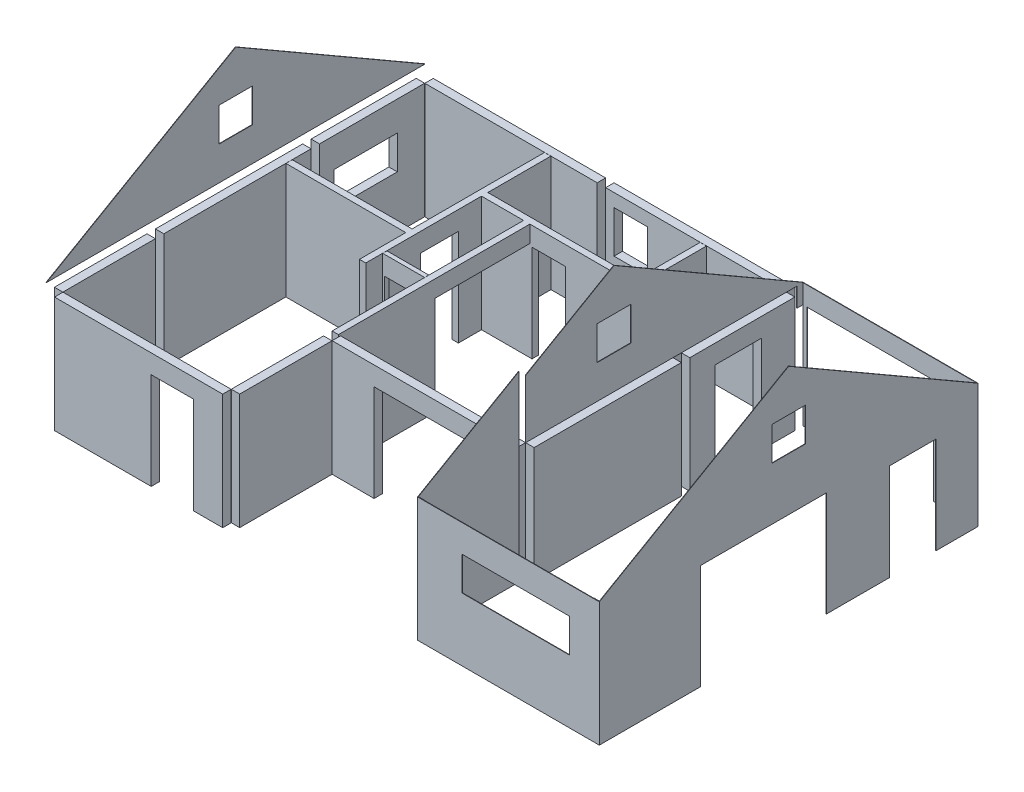
SolidWorks part; units mm, degrees
ref_plane "Спереди" through (0, 0, 0) normal (0, 0, 1) x (1, 0, 0)
ref_plane "Сверху" through (0, 0, 0) normal (0, 1, 0) x (1, 0, 0)
ref_plane "Справа" through (0, 0, 0) normal (1, 0, 0) x (0, 0, -1)
sketch "Эскиз1" plane through (0, 0, 0) normal (0, 1, 0) x (1, 0, 0)
  line L0 (9000, -6600) -> (4400, -6600) construction
  line L1 (0, 0) -> (9000, 0) construction
  line L2 (0, 0) -> (0, -8800) construction
  line L3 (0, -9000) -> (4400, -9000) construction
  line L4 (9000, 0) -> (9000, -6600) construction
  line L5 (4400, -6600) -> (4400, -9000) construction
  line L6 (8800, -203) -> (9000, -203)
  line L7 (203, 0) -> (4300, 0)
  line L8 (203, 0) -> (203, -200)
  line L9 (203, -200) -> (4300, -200)
  line L12 (0, -200) -> (0, -2700)
  line L14 (200, -200) -> (200, -2700)
  line L15 (203, -9000) -> (2500, -9000)
  line L16 (203, -9000) -> (203, -8800)
  line L17 (203, -8800) -> (2500, -8800)
  line L19 (4400, -8797) -> (4200, -8797)
  line L20 (4400, -8797) -> (4400, -6603)
  line L22 (4200, -8797) -> (4200, -6603)
  line L24 (9000, -203) -> (9000, -1000)
  line L26 (8800, -203) -> (8800, -1000)
  line L27 (8797, -6600) -> (7597, -6600)
  line L28 (8797, -6600) -> (8797, -6400)
  line L29 (8797, -6400) -> (7597, -6400)
  line L31 (2500, -8800) -> (2500, -9000)
  line L32 (3500, -8800) -> (3500, -9000)
  line L33 (3500, -8800) -> (4200, -8800)
  line L34 (3500, -9000) -> (4200, -9000)
  line L35 (5597, -6400) -> (5597, -6600)
  line L36 (7597, -6400) -> (7597, -6600)
  line L37 (5597, -6400) -> (4400, -6400)
  line L38 (5597, -6600) -> (4400, -6600)
  line L39 (8800, -1000) -> (9000, -1000)
  line L41 (8800, -2100) -> (9000, -2100)
  line L42 (8800, -2100) -> (8800, -2700)
  line L43 (9000, -2100) -> (9000, -2700)
  line L47 (4200, -6400) -> (4350, -6400)
  line L83 (4200, -6603) -> (4400, -6603)
  line L92 (4200, -4100) -> (4350, -4100)
  line L93 (4200, -4100) -> (4200, -6400)
  line L94 (4350, -4100) -> (4350, -6400)
  line L100 (200, -8800) -> (0, -8800)
  line L101 (4200, -8800) -> (4200, -9000)
  line L102 (4400, -6400) -> (4400, -6600)
  line L103 (8800, -6400) -> (9000, -6400)
  line L104 (0, -200) -> (200, -200)
  line L108 (0, -4500) -> (0, -6400)
  line L109 (200, -4500) -> (200, -6400)
  line L110 (8800, 0) -> (8800, -200)
  line L111 (4300, 0) -> (4300, -200)
  line L113 (4500, 0) -> (4500, -200)
  line L114 (4500, 0) -> (8800, 0)
  line L115 (4500, -200) -> (8800, -200)
  line L116 (0, -9000) -> (0, -8800) construction
  line L117 (-6170.9643, 0) -> (12200, 0) construction
  line L118 (0, 1882.3698) -> (0, -11726.3327) construction
  line L119 (-6170.9643, -4500) -> (10764.3505, -4500) construction
  line L120 (1000, -4500) -> (2250, -4500) construction
  line L121 (-6170.9643, -9000) -> (12200, -9000) construction
  line L122 (1000, -4500) -> (1000, -4600) construction
  line L123 (1000, -4600) -> (2250, -4600) construction
  line L124 (2250, -4500) -> (2250, -4600) construction
  line L125 (1000, -4500) -> (2250, -4600) construction
  line L126 (1000, -4600) -> (2250, -4500) construction
  line L131 (0, -2700) -> (200, -2700)
  line L132 (0, -2900) -> (0, -4500)
  line L137 (3050, -203) -> (3200, -203)
  line L138 (3050, -203) -> (3050, -2400)
  line L139 (3050, -2400) -> (3200, -2400)
  line L140 (3200, -203) -> (3200, -1700)
  line L141 (3050, -203) -> (3200, -2400) construction
  line L142 (3050, -2400) -> (3200, -203) construction
  line L143 (3050, -3300) -> (3200, -3300)
  line L144 (3050, -3300) -> (3050, -3350)
  line L145 (3050, -4600) -> (3200, -4600)
  line L146 (3200, -3300) -> (3200, -4600)
  line L147 (3050, -3300) -> (3200, -4600) construction
  line L148 (3050, -4600) -> (3200, -3300) construction
  line L149 (4150, -4100) -> (4197, -4100)
  line L150 (4150, -4100) -> (4150, -4200)
  line L151 (4150, -4200) -> (4197, -4200)
  line L152 (4197, -4100) -> (4197, -4200)
  line L153 (4150, -4100) -> (4197, -4200) construction
  line L154 (4150, -4200) -> (4197, -4100) construction
  line L155 (203, -3350) -> (3050, -3350)
  line L156 (203, -3350) -> (203, -3500)
  line L157 (203, -3500) -> (3050, -3500)
  line L159 (203, -3350) -> (3050, -3500) construction
  line L160 (203, -3500) -> (3050, -3350) construction
  line L161 (6400, -3500) -> (8800, -3500) construction
  line L162 (4400, 2182.3698) -> (4400, -11426.3327) construction
  line L163 (5200, -1700) -> (6750, -1700)
  line L164 (9000, 2182.3698) -> (9000, -11265.4622) construction
  line L165 (5200, -1700) -> (5200, -1850)
  line L166 (5200, -1850) -> (6900, -1850)
  line L167 (6900, -1700) -> (6900, -1850)
  line L168 (5200, -1700) -> (6900, -1850) construction
  line L169 (5200, -1850) -> (6900, -1700) construction
  line L170 (5800, -2800) -> (8797, -2800) construction
  line L171 (5800, -2800) -> (5800, -2900) construction
  line L172 (5800, -2900) -> (8797, -2900) construction
  line L173 (8797, -2800) -> (8797, -2900) construction
  line L174 (5800, -2800) -> (8797, -2900) construction
  line L175 (5800, -2900) -> (8797, -2800) construction
  line L176 (6750, -203) -> (6900, -203)
  line L177 (6750, -203) -> (6750, -1700)
  line L179 (6900, -203) -> (6900, -1700)
  line L180 (6750, -203) -> (6900, -1700) construction
  line L181 (6750, -1700) -> (6900, -203) construction
  line L186 (3200, -1700) -> (4400, -1700)
  line L188 (3200, -1850) -> (4400, -1850)
  line L189 (4400, -1700) -> (4400, -1850)
  line L190 (3200, -1700) -> (4400, -1850) construction
  line L191 (3200, -1850) -> (4400, -1700) construction
  line L192 (5800, -2900) -> (6400, -2900) construction
  line L193 (5800, -2900) -> (5800, -3500) construction
  line L194 (5800, -3500) -> (6400, -3500) construction
  line L195 (6400, -2900) -> (6400, -3500) construction
  line L196 (5800, -2900) -> (6400, -3500) construction
  line L197 (5800, -3500) -> (6400, -2900) construction
  line L198 (12200, 0) -> (12200, -9000) construction
  line L199 (5350, -4400) -> (5800, -3500) construction
  line L204 (3203, -4100) -> (3250, -4100)
  line L205 (3203, -4100) -> (3203, -4200)
  line L206 (3203, -4200) -> (3250, -4200)
  line L207 (3250, -4100) -> (3250, -4200)
  line L208 (3203, -4100) -> (3250, -4200) construction
  line L209 (3203, -4200) -> (3250, -4100) construction
  line L210 (4350, -4400) -> (5350, -4400) construction
  line L211 (4350, -4400) -> (4350, -6400) construction
  line L212 (4350, -6400) -> (5350, -6400) construction
  line L213 (5350, -4400) -> (5350, -6400) construction
  line L214 (4350, -4400) -> (5350, -6400) construction
  line L215 (4350, -6400) -> (5350, -4400) construction
  line L216 (3200, -1850) -> (3200, -2400)
  line L217 (0, -2900) -> (200, -2900)
  line L218 (200, -2900) -> (200, -4500)
  line L219 (0, -6400) -> (200, -6400)
  line L220 (0, -6600) -> (0, -8800)
  line L221 (0, -6600) -> (200, -6600)
  line L222 (200, -6600) -> (200, -8800)
  line L223 (3050, -3500) -> (3050, -4600)
  line L224 (8800, -2700) -> (9000, -2700)
  line L225 (8800, -2900) -> (8800, -6400)
  line L226 (8800, -2900) -> (9000, -2900)
  line L227 (9000, -2900) -> (9000, -6400)
  point P14 (3226.5, -4150)
  point P17 (7298.5, -2850)
  point P41 (1625, -4550)
  point P52 (3125, -1301.5)
  point P62 (3125, -3950)
  point P67 (4173.5, -4150)
  point P72 (1626.5, -3425)
  point P103 (3800, -1775)
  point P104 (6825, -951.5)
  point P105 (4150, -4150)
  point P108 (6050, -1775)
  point P120 (6750, -951.5)
  point P122 (6100, -3200)
  point P127 (4850, -5400)
  dimension "D2" = 6600
  dimension "D3" = 9000
  dimension "D4" = 200
  dimension "D5" = 3
  dimension "D6" = 3
  dimension "D7" = 3
  dimension "D8" = 9000
  dimension "D9" = 200
  dimension "D10" = 3
  dimension "D11" = 3
  dimension "D12" = 700
  dimension "D13" = 50
  dimension "D14" = 4500
  dimension "D15" = 4000
  dimension "D16" = 100
  dimension "D17" = 800
  dimension "D18" = 4400
  dimension "D19" = 4600
  dimension "D20" = 1000
  dimension "D21" = 800
  dimension "D22" = 2000
  dimension "D23" = 1200
  dimension "D24" = 1100
  dimension "D25" = 3
  dimension "D26" = 200
  dimension "D27" = 1000
  dimension "D29" = 200
  dimension "D30" = 4500
  dimension "D31" = 3
  dimension "D32" = 200
  dimension "D33" = 3
  dimension "D34" = 900
  dimension "D35" = 3
  dimension "D36" = 900
  dimension "D37" = 50
  dimension "D38" = 150
  dimension "D39" = 100
  dimension "D40" = 3
  dimension "D41" = 2850
  dimension "D42" = 3150
  dimension "D43" = 1250
  dimension "D44" = 200
  dimension "D46" = 3550
  dimension "D47" = 1500
  dimension "D48" = 800
  dimension "D49" = 1900
  dimension "D50" = 950
  dimension "D51" = 3
  dimension "D53" = 800
  dimension "D54" = 3
  dimension "D55" = 4450
  dimension "D56" = 3500
  dimension "D57" = 2400
  dimension "D58" = 3000
  dimension "D59" = 1400
  dimension "D60" = 2650
  dimension "D61" = 600
  dimension "D63" = 2900
  dimension "D64" = 2300
  dimension "D65" = 1247
  dimension "D66" = 3200
  dimension "D67" = 2000
  dimension "D68" = 1000
  dimension "D72" = 200
extrude "Бобышка-Вытянуть3" add sketch "Эскиз1" along normal blind 2750 contours L155 | L42 L103 L43 L41 | L26 L39 L24 L6 | L113 L115 L110 L114 | L216 L188 L189 L186 L140 L137 L138 L139 | L179 L176 L177 L163 L165 L166 L167 | L157 L223 L145 L146 L143 L144 L155 L156 | L108 L219 L109 L218 L217 L132 | L222 L221 L220 L100 | L144 L145 L146 L143 | L140 L139 L138 L137 | L27 L36 L29 L28 | L8 L9 L111 L7 | L14 L131 L12 L104 | L100 L108 L132 L217 L218 L109 | L47 L94 L92 L93 | L35 L38 L102 L37 | L171 L172 L173 L170 | L19 L22 L83 L20 | L32 L34 L101 L33 | L15 L31 L17 L16 | L122 L120 L124 L123 | L205 L204 L207 L206 | L150 L149 L152 L151 | L165 L163 L167 L166 | L103 L227 L226 L225 region at (8900, 0, 601.5) region at (8900, 0, 2400) region at (100, 0, 7700) region at (100, 0, 4650) region at (6650, 0, 100) region at (3125, 0, 228.7863) region at (3125, 0, 3332.668) region at (5975, 0, 1723.6698)
sketch "Эскиз2" plane through (0, 0, 0) normal (-1, 0, 0) x (0, 0, 1)
  line L2 (850, 1250) -> (2350, 1250)
  line L3 (850, 1250) -> (850, 2050)
  line L4 (850, 2050) -> (2350, 2050)
  line L5 (2350, 1250) -> (2350, 2050)
  line L7 (200, 0) -> (2700, 0) construction
  line L8 (3350, 2750) -> (3350, 0) construction
  dimension "D1" = 1500
  dimension "D2" = 800
  dimension "D3" = 1250
  dimension "D4" = 1000
extrude "Вырез-Вытянуть2" cut sketch "Эскиз2" against normal blind 250
sketch "Эскиз3" plane through (0, 0, 0) normal (0, 0, -1) x (-1, 0, 0)
  line L0 (-4500, 0) -> (-8800, 0) construction
  line L8 (-5500, 2440) -> (-4700, 2440)
  line L9 (-5500, 2440) -> (-5500, 1440)
  line L10 (-5500, 1440) -> (-4700, 1440)
  line L11 (-4700, 2440) -> (-4700, 1440)
  line L15 (-4500, 2750) -> (-4500, 0) construction
  dimension "D1" = 200
  dimension "D2" = 2440
  dimension "D3" = 800
  dimension "D4" = 1000
  dimension "D5" = 1440
extrude "Вырез-Вытянуть3" cut sketch "Эскиз3" against normal blind 593
sketch "Эскиз4" plane through (0, 2750, 0) normal (0, 1, 0) x (1, 0, 0)
  line L6 (3203, -4100) -> (3250, -4100) construction
  line L7 (3226.5, -4100) -> (4173.5, -4100)
  line L8 (3226.5, -4100) -> (3226.5, -4200)
  line L9 (3226.5, -4200) -> (4173.5, -4200)
  line L10 (4173.5, -4100) -> (4173.5, -4200)
  line L11 (4150, -4200) -> (4197, -4200) construction
  line L13 (3050, -2346.4504) -> (3200, -2346.4504)
  line L14 (3050, -2346.4504) -> (3050, -3325)
  line L15 (3050, -3325) -> (3200, -3325)
  line L16 (3200, -2346.4504) -> (3200, -3325)
  line L19 (4249.5007, -1700) -> (5402.0861, -1700)
  line L20 (4249.5007, -1700) -> (4249.5007, -1850)
  line L21 (4249.5007, -1850) -> (5402.0861, -1850)
  line L22 (5402.0861, -1700) -> (5402.0861, -1850)
  line L24 (5200, -1850) -> (6900, -1850) construction
  line L29 (3050, -203) -> (3050, -2400) construction
  line L30 (5597, -6400) -> (4400, -6400) construction
  line L31 (5423.0031, -6400) -> (7690.4362, -6400)
  line L32 (5423.0031, -6400) -> (5423.0031, -6600)
  line L33 (5423.0031, -6600) -> (7690.4362, -6600)
  line L34 (7690.4362, -6400) -> (7690.4362, -6600)
  line L35 (8797, -6600) -> (7597, -6600) construction
  line L36 (8800, -203) -> (8800, -1000) construction
  line L37 (8800, -900.8258) -> (9000, -900.8258)
  line L38 (8800, -900.8258) -> (8800, -2153.976)
  line L39 (8800, -2153.976) -> (9000, -2153.976)
  line L40 (9000, -900.8258) -> (9000, -2153.976)
  line L41 (9000, -2100) -> (9000, -2700) construction
  line L42 (3500, -9000) -> (4200, -9000) construction
  line L43 (2379.0159, -8797) -> (3597.5552, -8797)
  line L44 (2379.0159, -8797) -> (2379.0159, -9000)
  line L45 (2379.0159, -9000) -> (3597.5552, -9000)
  line L46 (3597.5552, -8797) -> (3597.5552, -9000)
  line L47 (3200, -1850) -> (3200, -2400) construction
  line L48 (3200, -1700) -> (4400, -1700) construction
extrude "Бобышка-Вытянуть4" add sketch "Эскиз4" against normal offset from surface (450 mm away) 2300 up to face at (8900, 0, 601.5)
ref_plane "Плоскость1" through (13000, 0, 0) normal (1, 0, 0) x (0, 0, -1)
sketch "Эскиз5" plane through (13000, 0, 0) normal (1, 0, 0) x (0, 0, -1)
  line L0 (-4500, 5721.2813) -> (-4500, -150) construction
  line L1 (-6600, -150) -> (0, -150) construction
  line L2 (-4500, 5548.0762) -> (-9000, 2950)
  line L3 (-9000, 2950) -> (-9000, 0)
  line L5 (0, 2950) -> (0, 0)
  line L6 (-4500, 5548.0762) -> (0, 2950)
  line L7 (-8800, 0) -> (-9000, 0) construction
  line L8 (-9000, 0) -> (-8750, 0) construction
  line L9 (-9000, 0) -> (0, 0)
extrude "Бобышка-Вытянуть5" add sketch "Эскиз5" along normal blind 150 separate body
sketch "Эскиз6" plane through (13000, 0, 0) normal (1, 0, 0) x (0, 0, -1)
  line L0 (-9000, 0) -> (0, 0) construction
  line L1 (-1000, 2300) -> (-2100, 2300)
  line L2 (-1000, 2300) -> (-1000, 0)
  line L3 (-1000, 0) -> (-2100, 0)
  line L4 (-2100, 2300) -> (-2100, 0)
  line L5 (0, 2494.3376) -> (50, 2494.3376) construction
  line L6 (-6600, -150) -> (-3600, -150)
  line L7 (-6600, -150) -> (-6600, 2494.3376)
  line L8 (-6600, 2494.3376) -> (-3600, 2494.3376)
  line L9 (-3600, -150) -> (-3600, 2494.3376)
  dimension "D1" = 3000
  dimension "D2" = 1100
extrude "Вырез-Вытянуть5" cut sketch "Эскиз6" along normal blind 670
sketch "Эскиз8" plane through (0, 0, 0) normal (-1, 0, 0) x (0, 0, 1)
  line L0 (4500, 5548.0762) -> (0, 2950)
  line L1 (0, 2950) -> (9000, 2950)
  line L2 (9000, 2950) -> (4500, 5548.0762)
  line L3 (4500, 5548.0762) -> (4500, 2950) construction
  line L4 (2350, 1250) -> (2350, 2050) construction
  line L5 (4100, 4550) -> (4900, 4550)
  line L6 (4100, 4550) -> (4100, 3750)
  line L7 (4100, 3750) -> (4900, 3750)
  line L8 (4900, 4550) -> (4900, 3750)
  dimension "D1" = 800
extrude "Бобышка-Вытянуть8" add sketch "Эскиз8" against normal blind 10 separate body
sketch "Эскиз9" plane through (9000, 0, 0) normal (1, 0, 0) x (0, 0, -1)
  line L0 (-6600, 0) -> (-6600, 2950)
  line L1 (-6600, 2750) -> (-6600, 0) construction
  line L2 (-6600, 2950) -> (0, 2950)
  line L3 (0, 2950) -> (-4500, 5548.0762)
  line L4 (-4500, 5548.0762) -> (-9000, 2950)
  line L5 (-9000, 2950) -> (-9000, 0)
  line L6 (-9000, 0) -> (-6600, 0)
extrude "Бобышка-Вытянуть9" add sketch "Эскиз9" against normal blind 170 separate body
sketch "Эскиз10" plane through (0, 0, 0) normal (0, -1, 0) x (1, 0, 0)
  line L0 (13000, 9000) -> (13000, 6600) construction
  line L1 (9000, 9000) -> (13000, 9000)
  line L2 (9000, 9000) -> (9000, 8850)
  line L3 (9000, 8850) -> (13000, 8850)
  line L4 (13000, 9000) -> (13000, 8850)
  line L5 (13150, 9000) -> (13000, 9000) construction
  line L6 (9000, 6600) -> (9000, 0) construction
  line L7 (13000, 0) -> (12100, 0)
  line L8 (13000, 0) -> (13000, 150)
  line L9 (13000, 150) -> (12100, 150)
  line L10 (12100, 0) -> (12100, 150)
  line L11 (9000, 150) -> (9100, 150)
  line L12 (9000, 150) -> (9000, 0)
  line L13 (9000, 0) -> (9100, 0)
  line L14 (9100, 150) -> (9100, 0)
extrude "Бобышка-Вытянуть10" add sketch "Эскиз10" against normal up to vertex (2950 mm away) up to point (9000, 2950, 9000)
sketch "Эскиз11" plane through (0, 0, 6400) normal (0, 0, -1) x (-1, 0, 0)
  line L0 (-203, 0) -> (-4300, 0) construction
  line L1 (-7597, 2300) -> (-5397, 2300)
  line L2 (-7597, 2300) -> (-7597, -335.5255)
  line L3 (-7597, -335.5255) -> (-5397, -335.5255)
  line L4 (-5397, 2300) -> (-5397, -335.5255)
  line L5 (-12440, 3005.7735) -> (-12440, 50) construction
  line L6 (-2500, 2300) -> (-3500, 2300)
  line L7 (-2500, 2300) -> (-2500, -123.1481)
  line L8 (-2500, -123.1481) -> (-3500, -123.1481)
  line L9 (-3500, 2300) -> (-3500, -123.1481)
  line L11 (-9890, 2300) -> (-12440, 2300)
  line L12 (-9890, 2300) -> (-9890, 1500)
  line L13 (-9890, 1500) -> (-12440, 1500)
  line L14 (-12440, 2300) -> (-12440, 1500)
  line L15 (-9000, 0) -> (-13000, 0) construction
  line L17 (-9890, 3005.7735) -> (-9890, 50) construction
  point P14 (0, 0)
  point P15 (-10032.0886, 1500)
  point P23 (0, 0)
  point P24 (-9890, 1500)
  point P26 (-9890, 1500)
  dimension "D1" = 1500
  dimension "D2" = 800
  dimension "D3" = 2200
  dimension "D4" = 2300
  dimension "D5" = 2550
extrude "Вырез-Вытянуть6" cut sketch "Эскиз11" against normal blind 5123
sketch "Эскиз12" plane through (0, 0, 0) normal (-1, 0, 0) x (0, 0, 1)
  line L0 (2424.8711, 2950) -> (2424.8711, 4350) construction
  line L1 (0, 2950) -> (9000, 2950) construction
  line L2 (4500, 5548.0762) -> (0, 2950) construction
  line L3 (2424.8711, 4350) -> (3290.8965, 4850) construction
  line L4 (3290.8965, 4850) -> (5709.1035, 4850) construction
  line L5 (9000, 2950) -> (4500, 5548.0762) construction
  line L6 (5709.1035, 4850) -> (6575.1289, 4350) construction
  line L7 (6575.1289, 4350) -> (6575.1289, 2950) construction
  line L8 (4500, 5548.0762) -> (4500, 4850) construction
  dimension "D1" = 1900
  dimension "D2" = 2418.2069
  dimension "D3" = 1400
  dimension "D4" = 4150.2577
extrude "Вырез-Вытянуть7" cut sketch "Эскиз8<2>" against normal blind 16606 contours L5 L8 L7 L6
sketch "Эскиз8<2>" plane through (0, 0, 0) normal (-1, 0, 0) x (0, 0, 1) same geometry as "Эскиз8"
sketch "Эскиз13" plane through (0, 0, 0) normal (-1, 0, 0) x (0, 0, 1)
  line L0 (4500, 5548.0762) -> (0, 2950)
  line L1 (0, 2950) -> (0, 0)
  line L2 (0, 0) -> (9000, 0)
  line L3 (9000, 2950) -> (9000, 0) construction
  line L4 (4500, 5548.0762) -> (9000, 2950)
  line L5 (9000, 2950) -> (9000, 0)
  line L7 (4100, 4550) -> (4900, 4550)
  line L8 (4100, 4550) -> (4100, 3750)
  line L9 (4100, 3750) -> (4900, 3750)
  line L10 (4900, 4550) -> (4900, 3750)
  line L11 (850, 2050) -> (2350, 2050)
  line L12 (850, 2050) -> (850, 1250)
  line L13 (850, 1250) -> (2350, 1250)
  line L14 (2350, 2050) -> (2350, 1250)
sketch "Эскиз16" plane through (13150, 0, 0) normal (1, 0, 0) x (0, 0, -1)
  line L0 (-150, 2950) -> (-150, 0) construction
  line L1 (0, 2950) -> (-150, 2950)
  line L2 (0, 2950) -> (0, 2494.3376)
  line L3 (0, 2494.3376) -> (-150, 2494.3376)
  line L4 (-150, 2950) -> (-150, 2494.3376)
  line L5 (-3600, 2494.3376) -> (-6600, 2494.3376) construction
extrude "Бобышка-Вытянуть16" add sketch "Эскиз16" against normal blind 4160
sketch "Эскиз17" plane through (0, 0, 4100) normal (0, 0, -1) x (-1, 0, 0)
  line L0 (-4200, 2750) -> (-4200, 0) construction
  line L1 (-4350, 2750) -> (-4200, 2750)
  line L2 (-4350, 2750) -> (-4350, 2350)
  line L3 (-4350, 2350) -> (-4200, 2350)
  line L4 (-4200, 2750) -> (-4200, 2350)
  dimension "D1" = 400
extrude "Бобышка-Вытянуть17" add sketch "Эскиз17" along normal up to surface (2250 mm away) up to face at (4925, 1262.5, 1850)
sketch "Эскиз18" plane through (0, 2750, 0) normal (0, 1, 0) x (1, 0, 0)
  line L0 (9000, -4500) -> (9000, -9000) construction
  line L1 (8644.5298, 46.0605) -> (8990, 46.0605)
  line L2 (8644.5298, 46.0605) -> (8644.5298, -6600)
  line L3 (8644.5298, -6600) -> (8990, -6600)
  line L4 (8990, 46.0605) -> (8990, -6600)
  line L5 (8797, -6600) -> (4400, -6600) construction
  line L6 (13000, -9000) -> (9000, -9000) construction
  line L7 (9392.4652, -10) -> (13140, -10)
  line L8 (9392.4652, -10) -> (9392.4652, -8990)
  line L9 (9392.4652, -8990) -> (13140, -8990)
  line L10 (13140, -10) -> (13140, -8990)
  line L11 (13150, -4500) -> (13150, -9000) construction
  line L12 (9000, 0) -> (13000, 0) construction
  dimension "D1" = 10
  dimension "D2" = 10
  dimension "D3" = 10
  dimension "D4" = 10
extrude "Вырез-Вытянуть8" cut sketch "Эскиз18" along normal blind 5414
sketch "Эскиз19" plane through (0, 0, 0) normal (0, -1, 0) x (1, 0, 0)
  line L0 (8990, 6600) -> (8830, 6600) construction
  line L1 (8840, 6600) -> (11709.562, 6600)
  line L2 (8840, 6600) -> (8840, 8990)
  line L3 (8840, 8990) -> (13140, 8990)
  line L4 (13140, 6600) -> (13140, 8990)
  line L5 (8797, 6600) -> (4400, 6600) construction
  line L6 (8830, 6600) -> (8830, 9000) construction
  line L7 (8830, 9000) -> (9000, 9000) construction
  line L8 (13140, 8990) -> (13140, 10) construction
  line L9 (9000, 10) -> (13140, 10)
  line L10 (13140, 10) -> (13140, 6600)
  line L11 (13140, 10) -> (9392.4652, 10) construction
  line L12 (9000, 0) -> (9000, 150) construction
  line L13 (9000, 10) -> (9000, 150)
  line L14 (9000, 150) -> (11709.562, 6600)
  dimension "D1" = 10
  dimension "D2" = 10
extrude "Вырез-Вытянуть9" cut sketch "Эскиз19" against normal blind 5663
